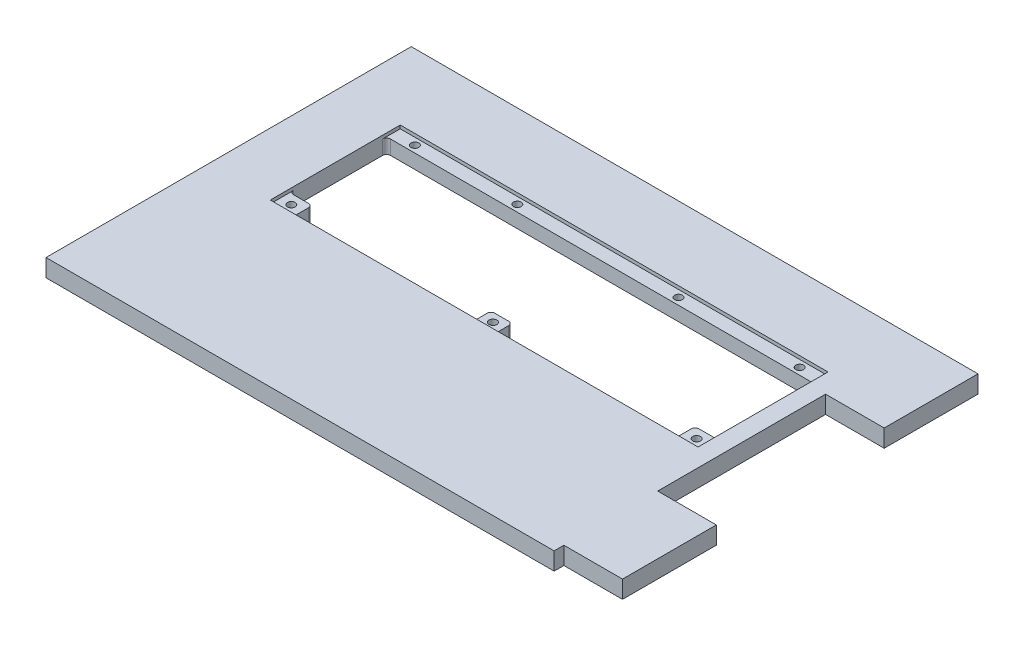
SolidWorks part; units mm, degrees
ref_plane "Front Plane" through (0, 0, 0) normal (0, 0, 1) x (1, 0, 0)
ref_plane "Top Plane" through (0, 0, 0) normal (0, 1, 0) x (1, 0, 0)
ref_plane "Right Plane" through (0, 0, 0) normal (1, 0, 0) x (0, 0, -1)
sketch "Sketch1" plane through (0, 0, 0) normal (0, 1, 0) x (1, 0, 0)
  line L1 (-15, 0) -> (245, 0)
  line L2 (-15, 0) -> (-15, 186.9)
  line L3 (-15, 186.9) -> (245, 186.9)
  line L4 (245, 0) -> (245, 186.9)
  point P4 (0, 0)
  dimension "D1" = 186.9
  dimension "D2" = 260
extrude "Boss-Extrude1" add sketch "Sketch1" along normal blind 9
sketch "Sketch2" plane through (0, 0, 0) normal (0, 1, 0) x (1, 0, 0)
  line L0 (245, 186.9) -> (-15, 186.9) construction
  line L1 (16.91, 149.35) -> (235.81, 149.35)
  line L2 (16.91, 149.35) -> (16.91, 82.85)
  line L3 (16.91, 82.85) -> (235.81, 82.85)
  line L4 (235.81, 149.35) -> (235.81, 82.85)
  dimension "D1" = 37.55
  dimension "D3" = 66.5
  dimension "D4" = 218.9
extrude "Cut-Extrude1" cut sketch "Sketch2" along normal blind 9
sketch "Sketch3" plane through (0, 9, 0) normal (0, 1, 0) x (1, 0, 0)
  line L0 (235.81, 149.35) -> (16.91, 149.35) construction
  line L1 (16.91, 149.35) -> (16.91, 82.85) construction
  line L2 (16.91, 82.85) -> (235.81, 82.85) construction
  circle A0 centre (27.91, 145.85) radius 2
  circle A1 centre (80.31, 145.85) radius 2
  circle A2 centre (162.81, 145.85) radius 2
  circle A3 centre (224.81, 145.85) radius 2
  circle A4 centre (22.66, 87.85) radius 2
  circle A5 centre (126.36, 87.35) radius 2
  circle A6 centre (230.06, 87.85) radius 2
  dimension "D3" = 4
  dimension "D4" = 3.5
  dimension "D6" = 3.5
  dimension "D8" = 3.5
  dimension "D10" = 5
  dimension "D12" = 4.5
  dimension "D14" = 5
  dimension "D1" = 3.5
  dimension "D2" = 11
  dimension "D5" = 52.4
  dimension "D7" = 82.5
  dimension "D9" = 62
  dimension "D11" = 5.75
  dimension "D13" = 103.7
  dimension "D15" = 103.7
sketch "Sketch4" plane through (0, 0, 0) normal (0, 1, 0) x (1, 0, 0)
  line L0 (235.81, 82.85) -> (235.81, 149.35) construction
  line L1 (16.91, 149.35) -> (235.81, 149.35)
  line L2 (16.91, 149.35) -> (16.91, 142.35)
  line L3 (16.91, 142.35) -> (235.81, 142.35)
  line L4 (235.81, 149.35) -> (235.81, 142.35)
  line L5 (16.91, 82.85) -> (235.81, 82.85) construction
  line L6 (235.81, 82.85) -> (224.31, 82.85)
  line L7 (235.81, 82.85) -> (235.81, 92.85)
  line L8 (235.81, 92.85) -> (224.31, 92.85)
  line L9 (224.31, 82.85) -> (224.31, 92.85)
  line L10 (120.86, 82.85) -> (131.86, 82.85)
  line L11 (120.86, 82.85) -> (120.86, 91.85)
  line L12 (120.86, 91.85) -> (131.86, 91.85)
  line L13 (131.86, 82.85) -> (131.86, 91.85)
  line L15 (16.91, 82.85) -> (28.41, 82.85)
  line L16 (16.91, 82.85) -> (16.91, 92.85)
  line L17 (16.91, 92.85) -> (28.41, 92.85)
  line L18 (28.41, 82.85) -> (28.41, 92.85)
  dimension "D1" = 7
  dimension "D2" = 5
  dimension "D3" = 5.75
  dimension "D4" = 4.5
  dimension "D5" = 5.5
  dimension "D6" = 5.5
  dimension "D7" = 5.75
  dimension "D8" = 5
extrude "Boss-Extrude2" add sketch "Sketch4" along normal blind 7.3
extrude "Cut-Extrude2" cut sketch "Sketch3" against normal blind 6.6
fillet "Fillet1" radius 2 12 edges at (16.91, 3.65, -92.85) (28.41, 3.65, -82.85) (28.41, 3.65, -92.85) (16.91, 3.65, -142.35) (235.81, 3.65, -142.35) (235.81, 3.65, -92.85) (224.31, 3.65, -82.85) (224.31, 3.65, -92.85) (120.86, 3.65, -82.85) (131.86, 3.65, -82.85) (131.86, 3.65, -91.85) (120.86, 3.65, -91.85)
sketch "Sketch5" plane through (245, 0, 0) normal (1, 0, 0) x (0, 0, -1)
  line L0 (0, 0) -> (186.9, 0) construction
  line L1 (5, 9) -> (53, 9)
  line L2 (5, 9) -> (5, 0)
  line L3 (5, 0) -> (53, 0)
  line L4 (53, 9) -> (53, 0)
  line L6 (186.9, 9) -> (138.9, 9)
  line L7 (186.9, 9) -> (186.9, 0)
  line L8 (186.9, 0) -> (138.9, 0)
  line L9 (138.9, 9) -> (138.9, 0)
  point P12 (0, 0)
  point P13 (0, 0)
  point P14 (0, 0)
  dimension "D1" = 48
  dimension "D2" = 48
extrude "Boss-Extrude3" add sketch "Sketch5" along normal blind 30
